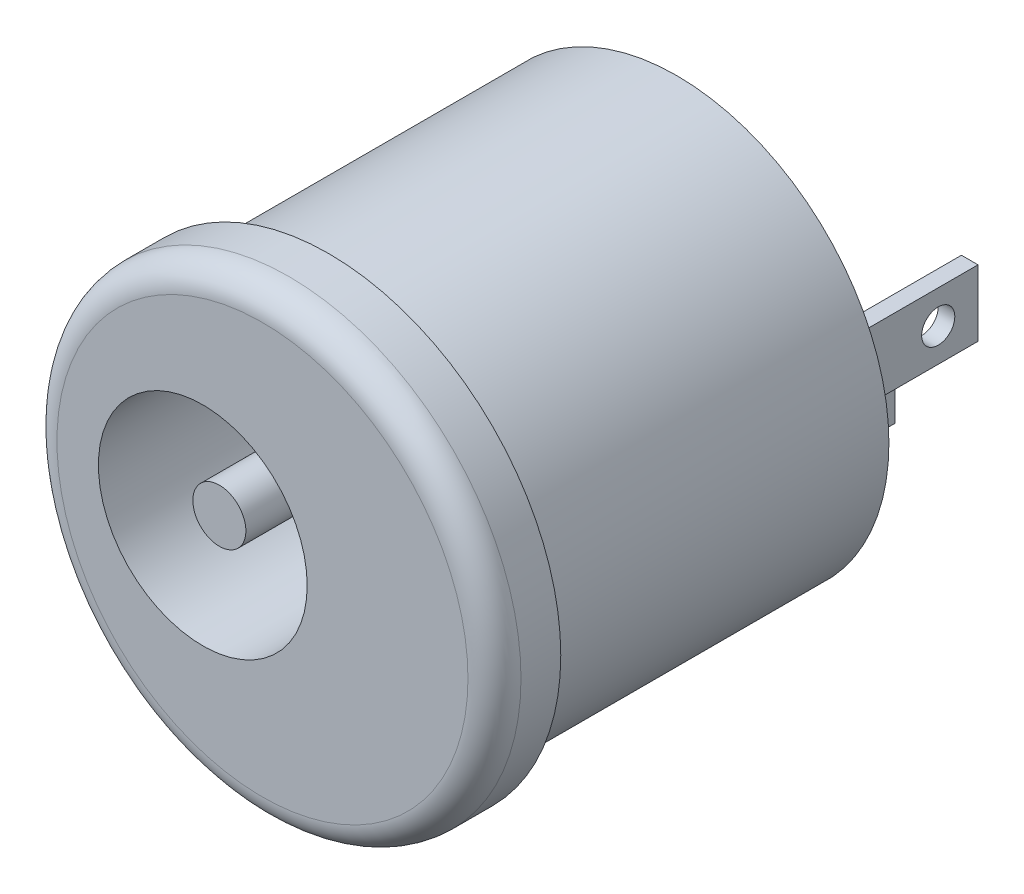
SolidWorks part; units mm, degrees
ref_plane "Plan de face" through (0, 0, 0) normal (0, 0, 1) x (1, 0, 0)
ref_plane "Plan de dessus" through (0, 0, 0) normal (0, 1, 0) x (1, 0, 0)
ref_plane "Plan de droite" through (0, 0, 0) normal (1, 0, 0) x (0, 0, -1)
sketch "Esquisse1" plane through (0, 0, 0) normal (0, 0, 1) x (1, 0, 0)
  circle A0 centre (0, 0) radius 7
extrude "Boss.-Extru.1" add sketch "Esquisse1" along normal blind 12.5
sketch "Esquisse2" plane through (0, 0, 0) normal (0, 0, -1) x (-1, 0, 0)
  circle A0 centre (0, 0) radius 6.4
  circle A1 centre (0, 0) radius 7
extrude "Enlèv. mat.-Extru.1" cut sketch "Esquisse2" against normal blind 10.5
sketch "Esquisse4" plane through (0, 0, 12.5) normal (0, 0, 1) x (1, 0, 0)
  circle A0 centre (-1.8, 0) radius 3.15
  point P2 (0, 0)
  dimension "D1" = 1.8
extrude "Enlèv. mat.-Extru.3" cut sketch "Esquisse4" against normal blind 9
sketch "Esquisse5" plane through (0, 0, 3.5) normal (0, 0, 1) x (1, 0, 0)
  circle A0 centre (-1.8, 0) radius 0.8
  point P0 (-1.8, 0)
extrude "Boss.-Extru.2" add sketch "Esquisse5" along normal blind 8.5
sketch "Esquisse6" plane through (0, 0, 0) normal (0, 0, -1) x (-1, 0, 0)
  line L1 (-3.5874, 1) -> (-4.0874, 1)
  line L2 (-3.5874, 1) -> (-3.5874, -1)
  line L3 (-3.5874, -1) -> (-4.0874, -1)
  line L4 (-4.0874, 1) -> (-4.0874, -1)
  line L5 (-3.5874, 1) -> (-4.0874, -1) construction
  line L6 (-3.5874, -1) -> (-4.0874, 1) construction
  line L7 (-1.0872, -2.3899) -> (-1.5872, -2.3899)
  line L8 (-1.0872, -2.3899) -> (-1.0872, -4.3899)
  line L9 (-1.0872, -4.3899) -> (-1.5872, -4.3899)
  line L10 (-1.5872, -2.3899) -> (-1.5872, -4.3899)
  line L11 (-1.0872, -2.3899) -> (-1.5872, -4.3899) construction
  line L12 (-1.0872, -4.3899) -> (-1.5872, -2.3899) construction
  point P0 (-3.8374, 0)
  point P5 (-1.3372, -3.3899)
  dimension "D1" = 3.8374
  dimension "D2" = 2
  dimension "D3" = 0.5
  dimension "D4" = 2
  dimension "D5" = 0.5
extrude "Boss.-Extru.3" add sketch "Esquisse6" along normal blind 5
sketch "Esquisse7" plane through (1.5872, 0, 0) normal (1, 0, 0) x (0, 0, -1)
  line L0 (5, -4.3899) -> (0, -4.3899) construction
  line L1 (5, -2.3899) -> (5, -4.3899) construction
  circle A0 centre (3.8, -3.3899) radius 0.5
  dimension "D2" = 1.2
  dimension "D1" = 1
extrude "Enlèv. mat.-Extru.4" cut sketch "Esquisse7" against normal through all
sketch "Esquisse8" plane through (4.0874, 0, 0) normal (1, 0, 0) x (0, 0, -1)
  line L0 (5, 1) -> (5, -1) construction
  line L1 (5, -1) -> (0, -1) construction
  circle A0 centre (3.8, 0) radius 0.5
  point P2 (5, 0)
  dimension "D1" = 1.2
  dimension "D2" = 1
extrude "Enlèv. mat.-Extru.5" cut sketch "Esquisse8" against normal through all
fillet "Congé7" radius 0.8 1 edges at (7, 0, 12.5)
